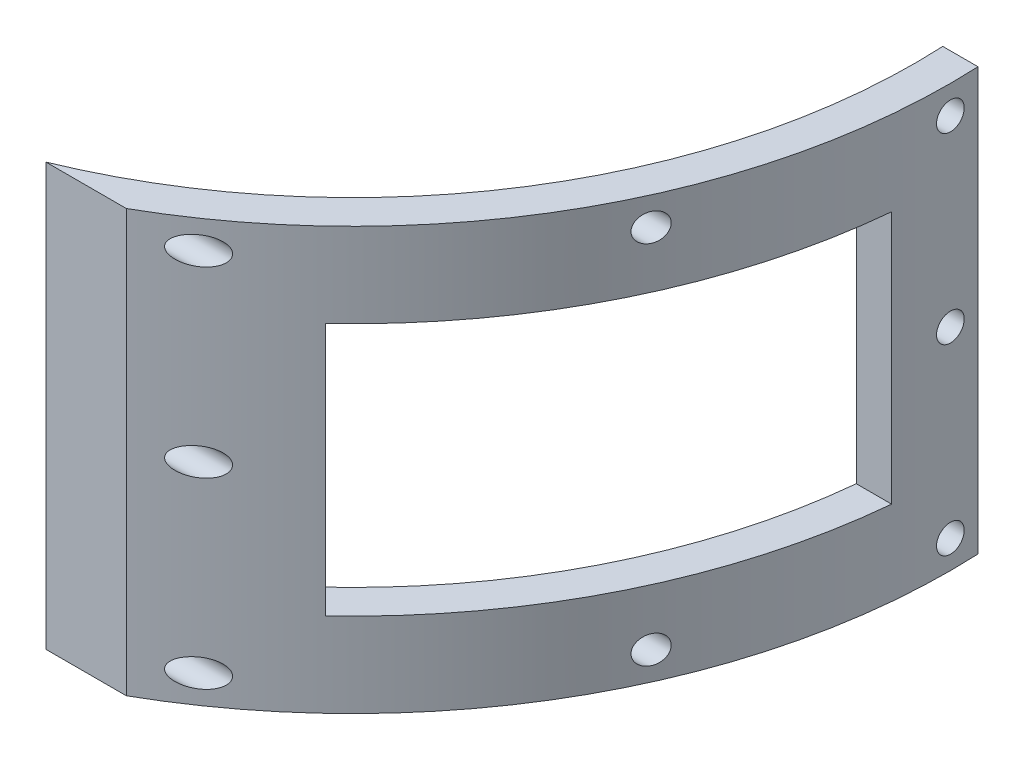
SolidWorks part; units mm, degrees
ref_plane "Front Plane" through (0, 0, 0) normal (0, 0, 1) x (1, 0, 0)
ref_plane "Top Plane" through (0, 0, 0) normal (0, 1, 0) x (1, 0, 0)
ref_plane "Right Plane" through (0, 0, 0) normal (1, 0, 0) x (0, 0, -1)
sketch "Sketch1" plane through (0, 0, 0) normal (0, 1, 0) x (1, 0, 0)
  circle A0 centre (0, 0) radius 101.6
sketch "Sketch2" plane through (0, 0, 0) normal (1, 0, 0) x (0, 0, -1)
  line L0 (-83.82, -5.08) -> (-83.82, -60.96)
  line L5 (-5.08, -60.96) -> (-83.82, -60.96)
  line L6 (-5.08, -5.08) -> (-5.08, -60.96)
  line L7 (-5.08, -5.08) -> (-83.82, -5.08)
  line L8 (-93.98, 5.08) -> (-93.98, -71.12)
  line L9 (5.08, -71.12) -> (-93.98, -71.12)
  line L10 (5.08, 5.08) -> (5.08, -71.12)
  line L11 (5.08, 5.08) -> (-93.98, 5.08)
  line L12 (-78.74, -10.16) -> (-78.74, -55.88)
  line L13 (-10.16, -55.88) -> (-78.74, -55.88)
  line L15 (-10.16, -10.16) -> (-10.16, -55.88)
  line L16 (-10.16, -10.16) -> (-78.74, -10.16)
  circle A0 centre (-88.9, 0) radius 2.5
  circle A1 centre (-44.45, 0) radius 2.5
  circle A2 centre (0, 0) radius 2.5
  circle A3 centre (-88.9, -33.02) radius 2.5
  circle A4 centre (-88.9, -66.04) radius 2.5
  circle A5 centre (-44.45, -66.04) radius 2.5
  circle A6 centre (0, -66.04) radius 2.5
  circle A7 centre (0, -33.02) radius 2.5
  dimension "D1" = 5.08
extrude "Boss-Extrude1" add sketch "Sketch2" along normal blind 203.2 contours L6 L7 L0 L5 L16 L15 L13 L12 region at (0, -6.0455, 44.45)
extrude "Boss-Extrude2" add sketch "Sketch2<3>" along normal blind 107.95 contours L10 L11 L8 L9 A7 A6 A5 A4 A3 A2 A1 A0 L7 L6 L5 L0 region at (0, 3.8302, 44.45)
sketch "Sketch2<3>" plane through (0, 0, 0) normal (1, 0, 0) x (0, 0, -1) same geometry as "Sketch2"
extrude "Cut-Extrude1" cut sketch "Sketch1" against normal through all both and the other way through all
sketch "Sketch3" plane through (0, 0, 0) normal (0, 1, 0) x (1, 0, 0)
  circle A1 centre (0, 0) radius 107.95
  circle A2 centre (0, 0) radius 615.95
  dimension "D1" = 508
extrude "Cut-Extrude3" cut sketch "Sketch3" against normal through all both and the other way through all contours A2 A1 region at (-598.5283, 0, 0)
